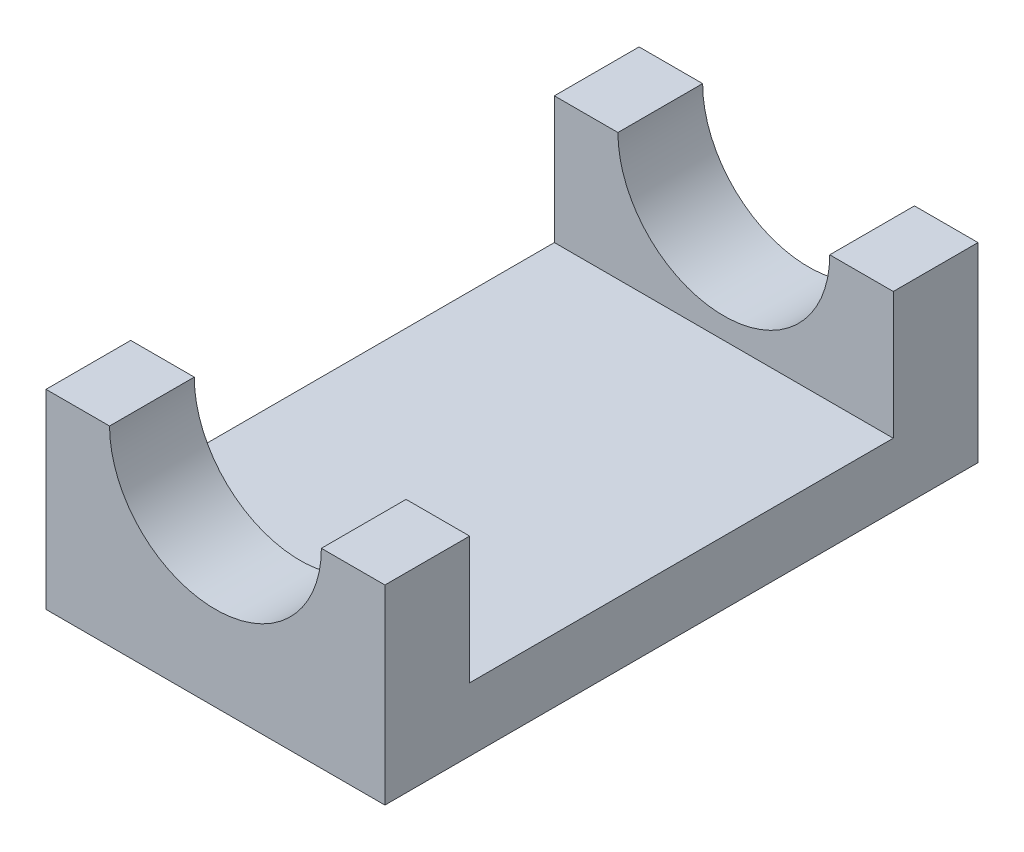
SolidWorks part; units mm, degrees
ref_plane "Front Plane" through (0, 0, 0) normal (0, 0, 1) x (1, 0, 0)
ref_plane "Top Plane" through (0, 0, 0) normal (0, 1, 0) x (1, 0, 0)
ref_plane "Right Plane" through (0, 0, 0) normal (1, 0, 0) x (0, 0, -1)
sketch "Sketch1" plane through (0, 0, 0) normal (0, 0, 1) x (1, 0, 0)
  line L1 (-20, 22.5) -> (20, 22.5)
  line L2 (-20, 22.5) -> (-20, -22.5)
  line L3 (-20, -22.5) -> (20, -22.5)
  line L4 (20, 22.5) -> (20, -22.5)
  line L5 (-20, 22.5) -> (20, -22.5) construction
  line L6 (-20, -22.5) -> (20, 22.5) construction
  point P0 (0, 0)
  dimension "D1" = 40
  dimension "D2" = 45
extrude "Boss-Extrude1" add sketch "Sketch1" along normal blind 70
sketch "Sketch2" plane through (0, 0, 0) normal (0, 0, -1) x (-1, 0, 0)
  circle A0 centre (0, 0) radius 12.5
  dimension "D1" = 25
extrude "Cut-Extrude1" cut sketch "Sketch2" against normal blind 10
ref_axis "Axis1" through (0, 0, 57.2332) along (0, 0, -1)
sketch "Sketch3" plane through (0, 0, 70) normal (0, 0, 1) x (1, 0, 0)
  circle A0 centre (0, 0) radius 12.5
  dimension "D1" = 25
extrude "Cut-Extrude2" cut sketch "Sketch3" against normal blind 10
sketch "Sketch4" plane through (0, 0, 70) normal (0, 0, 1) x (1, 0, 0)
  line L0 (-20, 0) -> (20, 0)
  line L1 (-20, 22.5) -> (-20, -22.5) construction
  line L2 (20, -22.5) -> (20, 22.5) construction
  line L3 (20, 22.5) -> (-20, 22.5) construction
  line L4 (20, 0) -> (20, 22.5)
  line L5 (-20, 22.5) -> (-20, 0)
  line L6 (20, 22.5) -> (-20, 22.5)
extrude "Cut-Extrude3" cut sketch "Sketch4" against normal through all
sketch "Sketch5" plane through (0, 0, 0) normal (0, 1, 0) x (1, 0, 0)
  line L0 (-20, 0) -> (-20, -70) construction
  line L1 (-20, -10) -> (20, -10)
  line L2 (-20, -10) -> (-20, -60)
  line L3 (-20, -60) -> (20, -60)
  line L4 (20, -10) -> (20, -60)
  line L5 (20, 0) -> (20, -70) construction
  line L6 (-20, 0) -> (-12.5, 0) construction
  line L7 (-20, -70) -> (-12.5, -70) construction
  point P12 (-16.25, -70)
  dimension "D1" = 10
  dimension "D2" = 10
extrude "Cut-Extrude4" cut sketch "Sketch5" against normal blind 15
